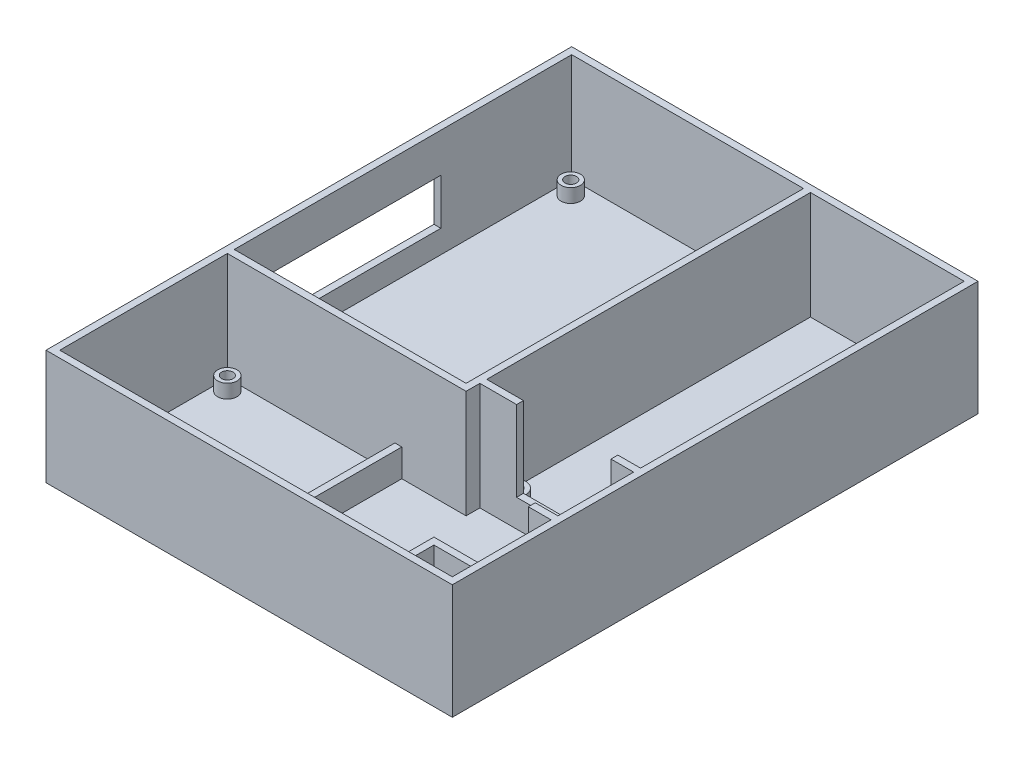
SolidWorks part; units mm, degrees
ref_plane "前视基准面" through (0, 0, 0) normal (0, 0, 1) x (1, 0, 0)
ref_plane "上视基准面" through (0, 0, 0) normal (0, 1, 0) x (1, 0, 0)
ref_plane "右视基准面" through (0, 0, 0) normal (1, 0, 0) x (0, 0, -1)
sketch "草图3" plane through (0, 0, 0) normal (0, 1, 0) x (1, 0, 0)
  line L0 (39.5, 1.5) -> (39.5, 38)
  line L1 (0, 0) -> (88.5, 0)
  line L2 (0, 0) -> (0, 114.5)
  line L3 (0, 114.5) -> (88.5, 114.5)
  line L4 (88.5, 0) -> (88.5, 114.5)
  line L5 (1.5, 38) -> (38, 38)
  line L6 (1.5, 38) -> (1.5, 1.5)
  line L7 (1.5, 1.5) -> (38, 1.5)
  line L8 (38, 38) -> (38, 1.5)
  line L9 (1.5, 113) -> (52, 113)
  line L10 (1.5, 113) -> (1.5, 39.5)
  line L11 (1.5, 39.5) -> (52, 39.5)
  line L12 (52, 113) -> (52, 39.5)
  line L13 (53.5, 113) -> (87, 113)
  line L14 (53.5, 113) -> (53.5, 42.5)
  line L15 (53.5, 42.5) -> (87, 42.5)
  line L16 (87, 113) -> (87, 42.5)
  line L17 (61.5, 23) -> (87, 23)
  line L18 (61.5, 23) -> (61.5, 1.5)
  line L19 (61.5, 1.5) -> (87, 1.5)
  line L20 (87, 23) -> (87, 1.5)
  line L21 (60, 1.5) -> (60, 24.5)
  line L22 (60, 24.5) -> (87, 24.5)
  line L23 (39.5, 38) -> (53.5, 38)
  line L24 (53.5, 38) -> (53.5, 41)
  line L25 (53.5, 41) -> (87, 41)
  line L26 (87, 41) -> (87, 24.5)
  line L27 (39.5, 1.5) -> (60, 1.5)
  circle A0 centre (4, 35.5) radius 2.1
  circle A1 centre (4, 35.5) radius 1.25
  circle A2 centre (4.5, 42.5) radius 2.1
  circle A3 centre (4.5, 42.5) radius 1.25
  circle A4 centre (49, 42.5) radius 2.1
  circle A5 centre (49, 42.5) radius 1.25
  circle A6 centre (49, 109.8) radius 2.1
  circle A7 centre (49, 109.8) radius 1.25
  circle A8 centre (4.5, 109.8) radius 2.1
  circle A9 centre (4.5, 109.8) radius 1.25
  circle A10 centre (84, 110) radius 2.5
  circle A11 centre (84, 110) radius 1.5
  circle A12 centre (56.5, 45.5) radius 2.5
  circle A13 centre (56.5, 45.5) radius 1.5
  circle A14 centre (65, 13.9) radius 2.5
  circle A15 centre (65, 13.9) radius 1.25
  dimension "D20" = 4.2
  dimension "D21" = 2.5
  dimension "D22" = 4.2
  dimension "D23" = 2.5
  dimension "D26" = 5
  dimension "D27" = 3
  dimension "D28" = 5
  dimension "D29" = 2.5
  dimension "D1" = 36.5
  dimension "D2" = 1.5
  dimension "D3" = 1.5
  dimension "D4" = 50.5
  dimension "D5" = 73.5
  dimension "D6" = 1.5
  dimension "D7" = 1.5
  dimension "D8" = 1.5
  dimension "D9" = 33.5
  dimension "D10" = 70.5
  dimension "D11" = 1.5
  dimension "D12" = 1.5
  dimension "D13" = 1.5
  dimension "D14" = 25.5
  dimension "D15" = 21.5
  dimension "D16" = 1.5
  dimension "D17" = 1.5
  dimension "D18" = 1.5
  dimension "D19" = 1.5
  dimension "D30" = 3.5
  dimension "D31" = 9.1
  dimension "D32" = 2.5
  dimension "D33" = 2.5
  dimension "D34" = 3
  dimension "D35" = 3
  dimension "D36" = 3
  dimension "D37" = 3
  dimension "D38" = 3
  dimension "D39" = 3
  dimension "D40" = 1.5
  dimension "D41" = 1.5
  dimension "D42" = 1.5
  dimension "D43" = 1.5
  dimension "D24" = 2
  dimension "D25" = 2
extrude "凸台-拉伸1" add sketch "草图3" along normal blind 25 contours L5 L8 L4 L3 L2 L1 L7 L6 L9 L12 L11 L10 L13 L16 L15 L14 L17 L20 L19 L18 region at (1.4472, 0, -57.25)
extrude "凸台-拉伸2" add sketch "草图3<3>" along normal blind 1.5 contours L20 L17 L18 L19 | L12 L9 L10 L11 A8 A6 A4 A2 | L8 L5 L6 L7 A0 | L16 L13 L14 L15 A12 A10 | L0 L27 L21 L22 L26 L25 L24 L23 region at (58.5834, 0, -24.841) region at (19.9155, 0, -19.5845) region at (26.75, 0, -76.2515) region at (70.25, 0, -77.75) region at (74.5936, 0, -12.1887)
sketch "草图3<3>" plane through (0, 0, 0) normal (0, 1, 0) x (1, 0, 0) same geometry as "草图3"
extrude "凸台-拉伸4" add sketch "草图3<5>" along normal blind 4.5 contours A0 A1 | A2 A3 | A4 A5 | A8 A9 | A6 A7 | A10 A11 | A12 A13 | A14 A15 region at (1.9594, 0, -35.5) region at (2.4594, 0, -42.5) region at (46.9594, 0, -42.5) region at (46.9594, 0, -109.8) region at (2.4594, 0, -109.8) region at (81.5707, 0, -110) region at (54.0707, 0, -45.5) region at (62.5707, 0, -13.9)
sketch "草图3<5>" plane through (0, 0, 0) normal (0, 1, 0) x (1, 0, 0) same geometry as "草图3"
sketch "草图4" plane through (0, 25, 0) normal (0, 1, 0) x (1, 0, 0)
  line L0 (38, 38) -> (38, 1.5) construction
  line L1 (61.5, 1.5) -> (38, 1.5)
  line L2 (61.5, 1.5) -> (61.5, 21.5023)
  line L3 (61.5, 38) -> (38, 38)
  line L4 (38, 1.5) -> (38, 38)
  line L6 (61.5, 44.9907) -> (82.0581, 44.9907)
  line L7 (61.5, 44.9907) -> (61.5, 38)
  line L8 (61.5, 21.5023) -> (82.0581, 21.5023)
  line L9 (39.5, 38) -> (53.5, 38) construction
  line L10 (82.0581, 44.9907) -> (82.0581, 21.5023)
extrude "切除-拉伸1" cut sketch "草图4" against normal offset from surface (17.5 mm away) 6 up to face at (4, 1.5, -33.4)
sketch "草图5" plane through (0, 0, 0) normal (-1, 0, 0) x (0, 0, 1)
  line L0 (-39.5, 25) -> (-39.5, 1.5) construction
  line L1 (-39.5, 25) -> (-39.5, 1.5) construction
  line L2 (-38, 25) -> (-38, 1.5) construction
  line L3 (-38, 25) -> (-38, 1.5) construction
  line L4 (-38, 1.5) -> (-1.5, 1.5) construction
  line L5 (-113, 1.5) -> (-39.5, 1.5) construction
  line L6 (-38, 1.5) -> (-1.5, 1.5) construction
  line L7 (-113, 1.5) -> (-39.5, 1.5) construction
  line L8 (-1.5, 25) -> (-1.5, 1.5) construction
  line L9 (-44.5, 6.5) -> (-84.5, 6.5)
  line L10 (-44.5, 6.5) -> (-44.5, 16.5)
  line L11 (-44.5, 16.5) -> (-84.5, 16.5)
  line L12 (-84.5, 6.5) -> (-84.5, 16.5)
  line L13 (-3.5, 6.5) -> (-14.5, 6.5)
  line L14 (-3.5, 6.5) -> (-3.5, 11.5)
  line L15 (-3.5, 11.5) -> (-14.5, 11.5)
  line L16 (-14.5, 6.5) -> (-14.5, 11.5)
  line L17 (-1.5, 25) -> (-1.5, 1.5) construction
  dimension "D1" = 40
  dimension "D2" = 10
  dimension "D3" = 5
  dimension "D4" = 5
  dimension "D5" = 5
  dimension "D6" = 11
  dimension "D7" = 2
  dimension "D8" = 5
extrude "切除-拉伸2" cut sketch "草图5" against normal up to next
